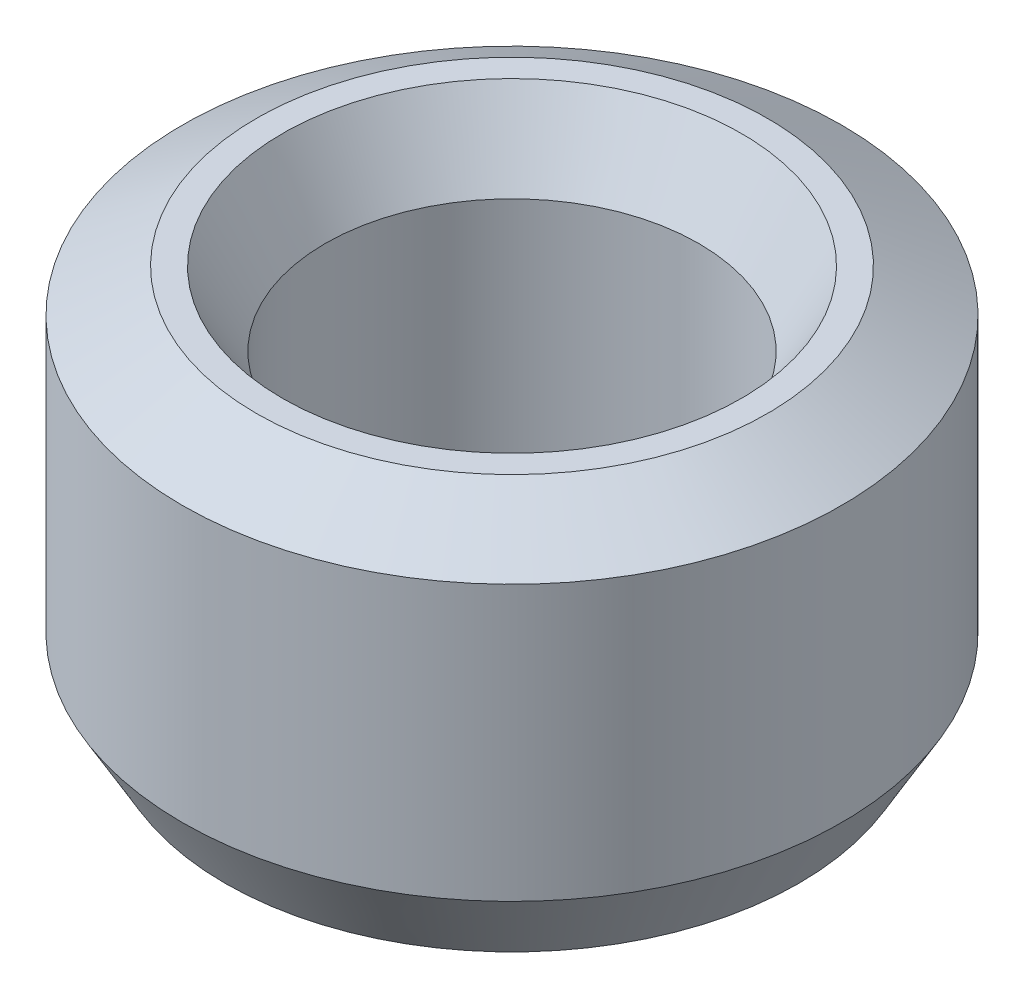
SolidWorks part; units mm, degrees
ref_plane "Front Plane" through (0, 0, 0) normal (0, 0, 1) x (1, 0, 0)
ref_plane "Top Plane" through (0, 0, 0) normal (0, 1, 0) x (1, 0, 0)
ref_plane "Right Plane" through (0, 0, 0) normal (1, 0, 0) x (0, 0, -1)
sketch "Sketch1" plane through (0, 0, 0) normal (0, 1, 0) x (1, 0, 0)
  circle A0 centre (0, 0) radius 17.5
  dimension "SLEEVE_OD" = 35
extrude "Boss-Extrude1" add sketch "Sketch1" along normal blind 20.7791
sketch "Sketch2" plane through (0, 0, 0) normal (0, 1, 0) x (1, 0, 0)
  circle A0 centre (0, 0) radius 9.9189
  dimension "BORE_D" = 19.8379
extrude "Cut-Extrude1" cut sketch "Sketch2" along normal through all
chamfer "Chamfer1" distance 2.267 angle 60 4 edges at (0, 20.7791, 9.9189) (0, 0, 9.9189) (0, 0, 17.5) (0, 20.7791, 17.5) first distance on face at (0, 20.7791, 9.9189) first distance on face at (0, 0, 9.9189) first distance on face at (0, 20.7791, 17.5)
